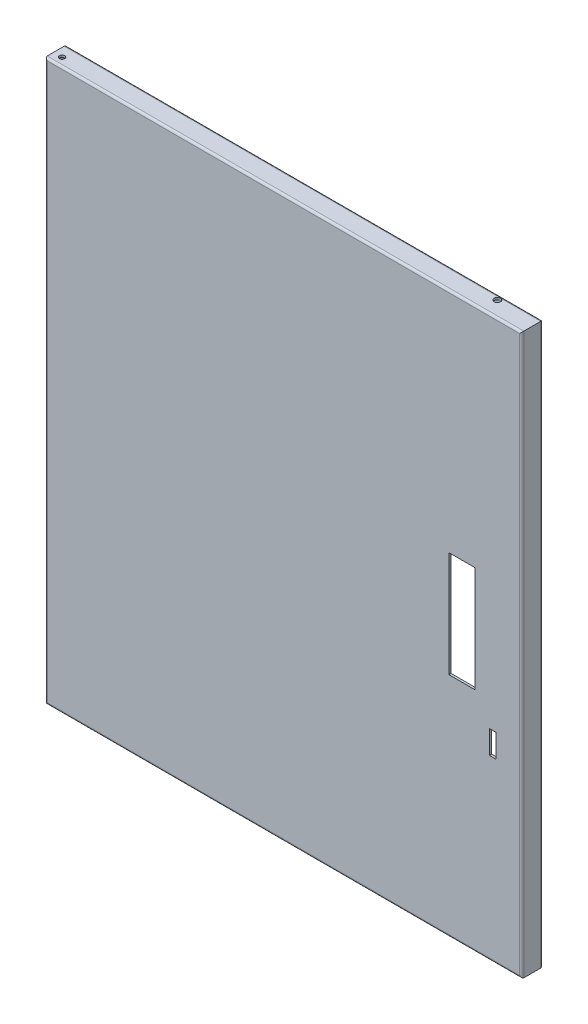
SolidWorks part; units mm, degrees
ref_plane "Front Plane" through (0, 0, 0) normal (0, 0, 1) x (1, 0, 0)
ref_plane "Top Plane" through (0, 0, 0) normal (0, 1, 0) x (1, 0, 0)
ref_plane "Right Plane" through (0, 0, 0) normal (1, 0, 0) x (0, 0, -1)
sketch "Sketch1" plane through (0, 0, 0) normal (0, 0, 1) x (1, 0, 0)
  line L1 (-225.5, 265) -> (225.5, 265)
  line L2 (-225.5, 265) -> (-225.5, -265)
  line L3 (-225.5, -265) -> (225.5, -265)
  line L4 (225.5, 265) -> (225.5, -265)
  line L5 (-225.5, 265) -> (225.5, -265) construction
  line L6 (-225.5, -265) -> (225.5, 265) construction
  point P0 (0, 0)
  dimension "D1" = 530
  dimension "D2" = 451
extrude "Boss-Extrude1" add sketch "Sketch1" along normal blind 20
sketch "Sketch2" plane through (0, 0, 0) normal (0, 0, -1) x (-1, 0, 0)
  line L0 (-225.5, 265) -> (225.5, 265) construction
  line L1 (-214.5, 254) -> (214.5, 254)
  line L2 (-214.5, 254) -> (-214.5, -254)
  line L3 (-214.5, -254) -> (214.5, -254)
  line L4 (214.5, 254) -> (214.5, -254)
  line L5 (225.5, 265) -> (225.5, -265) construction
  line L6 (225.5, -265) -> (-225.5, -265) construction
  line L7 (-225.5, -265) -> (-225.5, 265) construction
  dimension "D1" = 11
  dimension "D2" = 11
  dimension "D3" = 11
  dimension "D4" = 11
extrude "Cut-Extrude1" cut sketch "Sketch2" against normal blind 18
sketch "Sketch3" plane through (-214.5, 0, 0) normal (1, 0, 0) x (0, 0, -1)
  line L0 (-18, 254) -> (0, 254) construction
  line L1 (-18, -254) -> (-2, -254)
  line L2 (-18, -254) -> (-18, 254)
  line L3 (-18, 254) -> (-2, 254)
  line L4 (-2, -254) -> (-2, 254)
  line L5 (0, -254) -> (0, 254) construction
  dimension "D1" = 2
extrude "Cut-Extrude2" cut sketch "Sketch3" against normal blind 9
sketch "Sketch4" plane through (0, -254, 0) normal (0, 1, 0) x (1, 0, 0)
  line L0 (214.5, -18) -> (214.5, 0) construction
  line L1 (-223.5, -18) -> (214.5, -18)
  line L2 (-223.5, -18) -> (-223.5, -2)
  line L3 (-223.5, -2) -> (214.5, -2)
  line L4 (214.5, -18) -> (214.5, -2)
  line L5 (214.5, 0) -> (-214.5, 0) construction
  dimension "D1" = 2
extrude "Cut-Extrude3" cut sketch "Sketch4" against normal blind 9
sketch "Sketch5" plane through (214.5, 0, 0) normal (-1, 0, 0) x (0, 0, 1)
  line L0 (18, 254) -> (0, 254) construction
  line L1 (18, -263) -> (2, -263)
  line L2 (18, -263) -> (18, 254)
  line L3 (18, 254) -> (2, 254)
  line L4 (2, -263) -> (2, 254)
  line L5 (0, 254) -> (0, -254) construction
  dimension "D1" = 2
extrude "Cut-Extrude4" cut sketch "Sketch5" against normal blind 9
sketch "Sketch6" plane through (0, 254, 0) normal (0, -1, 0) x (1, 0, 0)
  line L0 (223.5, 18) -> (223.5, 2) construction
  line L1 (-223.5, 18) -> (223.5, 18)
  line L2 (-223.5, 18) -> (-223.5, 2)
  line L3 (-223.5, 2) -> (223.5, 2)
  line L4 (223.5, 18) -> (223.5, 2)
  line L5 (-214.5, 0) -> (214.5, 0) construction
  dimension "D1" = 2
extrude "Cut-Extrude5" cut sketch "Sketch6" against normal blind 9
sketch "Sketch7" plane through (0, 265, 0) normal (0, 1, 0) x (1, 0, 0)
  line L0 (225.5, -20) -> (-225.5, -20) construction
  line L1 (225.5, -20) -> (225.5, 0) construction
  circle A0 centre (217.5, -12) radius 2.5
  dimension "D1" = 5
  dimension "D2" = 8
  dimension "D3" = 8
sketch "Sketch8" plane through (0, 0, 20) normal (0, 0, 1) x (1, 0, 0)
  line L0 (-225.5, 265) -> (-225.5, -265) construction
  line L1 (-185.5, 55.5) -> (-152.5, 55.5)
  line L2 (-185.5, 55.5) -> (-185.5, -55.5)
  line L3 (-185.5, -55.5) -> (-152.5, -55.5)
  line L4 (-152.5, 55.5) -> (-152.5, -55.5)
  line L5 (225.5, 265) -> (-225.5, 265) construction
  point P8 (-152.5, 0)
  dimension "D1" = 73
  dimension "D2" = 111
  dimension "D3" = 33
  dimension "D4" = 265
fillet "Fillet3" radius 2 9 edges at (214.5, 0, 0) (225.5, 0, 0) (0, 265, 0) (0, -265, 0) (-225.5, 0, 0) (-225.5, 0, 20) (0, -265, 20) (225.5, 0, 20) (0, 265, 20)
fillet "Fillet4" radius 2 7 edges at (0, -263, 18) (223.5, 0, 18) (0, 263, 18) (-223.5, 0, 18) (-214.5, 0, 0) (1, -254, 0) (1, 254, 0)
sketch "Sketch12" plane through (0, 265, 0) normal (0, 1, 0) x (1, 0, 0)
  line L1 (-223.5, 0) -> (223.5, 0) construction
  line L2 (-225.5, -18) -> (-225.5, -2) construction
  circle A0 centre (-187.5, -5) radius 3
  dimension "D1" = 5
  dimension "D2" = 38
sketch "Sketch13" plane through (0, -265, 0) normal (0, -1, 0) x (1, 0, 0)
  line L0 (-225.5, 18) -> (-225.5, 2) construction
  line L1 (223.5, 0) -> (-223.5, 0) construction
  circle A0 centre (-150.5, 5) radius 3
  dimension "D1" = 75
  dimension "D2" = 5
sketch "Sketch20" plane through (0, 265, 0) normal (0, 1, 0) x (1, 0, 0)
  line L0 (-223.5, 0) -> (223.5, 0) construction
  line L1 (-225.5, -18) -> (-225.5, -2) construction
  circle A0 centre (-217.5, -12) radius 2.5
  dimension "D1" = 12
  dimension "D2" = 8
extrude "Cut-Extrude12" cut sketch "Sketch20" against normal through all
sketch "Sketch21" plane through (0, 265, 0) normal (0, 1, 0) x (1, 0, 0)
  line L0 (-223.5, 0) -> (223.5, 0) construction
  line L1 (225.5, -18) -> (225.5, -2) construction
  circle A0 centre (187.5, -5) radius 3
  dimension "D1" = 5
  dimension "D2" = 38
extrude "Cut-Extrude13" cut sketch "Sketch21" against normal up to surface (2 mm away) up to face at (-217.5, 263, 9.5)
sketch "Sketch22" plane through (0, -265, 0) normal (0, -1, 0) x (1, 0, 0)
  line L0 (225.5, 18) -> (225.5, 2) construction
  line L1 (223.5, 0) -> (-223.5, 0) construction
  circle A0 centre (150.5, 5) radius 3
  dimension "D1" = 75
  dimension "D2" = 5
extrude "Cut-Extrude14" cut sketch "Sketch22" against normal up to surface (2 mm away) up to face at (-217.5, -263, 9.5)
sketch "Sketch23" plane through (0, 0, 20) normal (0, 0, 1) x (1, 0, 0)
  line L0 (0, -8.376) -> (0, -59.5931)
  line L9 (201, -75) -> (195, -75)
  line L10 (201, -97) -> (201, -75)
  line L11 (201, -97) -> (195, -97)
  line L12 (195, -97) -> (195, -75)
  line L13 (181.5, 50) -> (156.5, 50)
  line L14 (156.5, -50) -> (156.5, 50)
  line L15 (181.5, -50) -> (156.5, -50)
  line L16 (181.5, -50) -> (181.5, 50)
extrude "Cut-Extrude15" cut sketch "Sketch23" against normal up to surface (2 mm away) contours L15 L16 L13 L14 | L12 L11 L10 L9 | L12 L9 L10 L11 region at (198, -86, 20) region at (169, 0, 20) up to face at (0, 0, 18)
